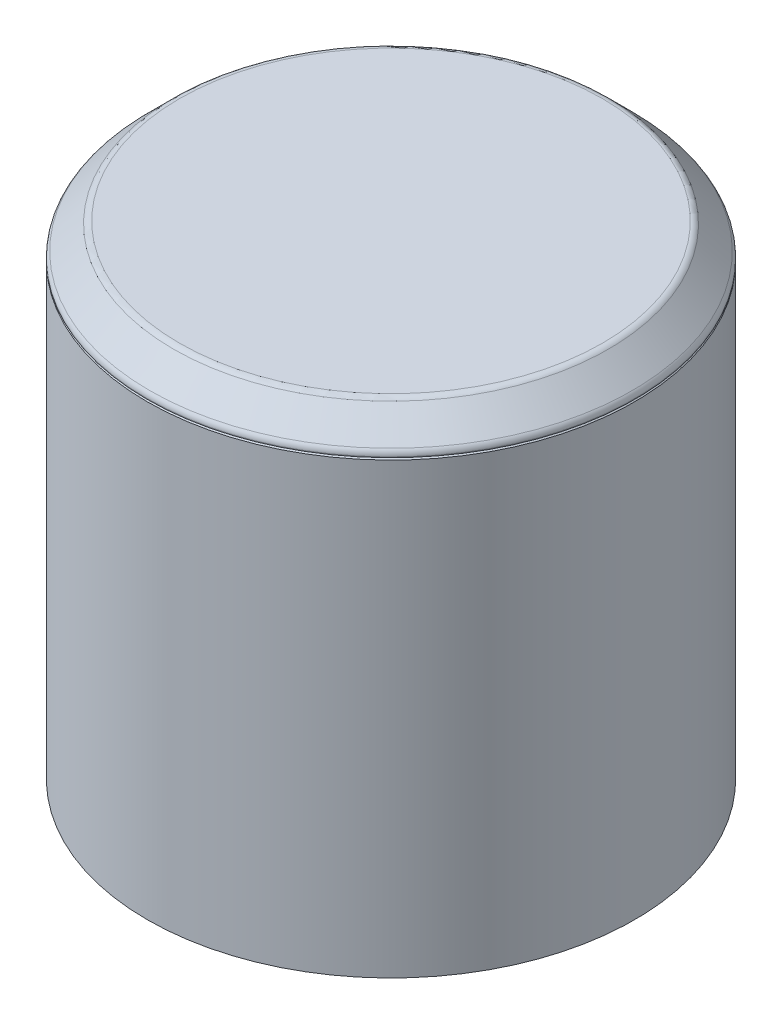
SolidWorks part; units mm, degrees
ref_plane "Ön Düzlem" through (0, 0, 0) normal (0, 0, 1) x (1, 0, 0)
ref_plane "Üst Düzlem" through (0, 0, 0) normal (0, 1, 0) x (1, 0, 0)
ref_plane "Sağ Düzlem" through (0, 0, 0) normal (1, 0, 0) x (0, 0, -1)
sketch "Çizim1" plane through (0, 0, 0) normal (1, 0, 0) x (0, 0, -1)
  line L1 (0, 0) -> (-59.5, 0)
  line L2 (0, 0) -> (0, 110)
  line L3 (0, 110) -> (-59.5, 110)
  line L4 (-59.5, 0) -> (-59.5, 110)
  line L5 (0, 0) -> (-45, 0)
  line L6 (0, 0) -> (0, -7)
  line L7 (0, -7) -> (-45, -7)
  line L8 (-45, 0) -> (-45, -7)
  dimension "D1" = 59.5
  dimension "D2" = 110
  dimension "D3" = 7
  dimension "D4" = 45
revolve "Döndür1" add sketch "Çizim1" angle 360 about L2 region at (0, -3.5, 22.5) region at (0, 55, 29.75)
sketch "Çizim2" plane through (0, 110, 0) normal (0, 1, 0) x (1, 0, 0)
  circle A0 centre (0, 0) radius 59.5
extrude "Yükseklik-Ekstrüzyon1" add sketch "Çizim2" along normal blind 8 separate body
chamfer "Pah1" distance 0.5 angle 45 1 edges at (0, 110, -59.5)
chamfer "Pah2" distance 7 angle 45 1 edges at (0, 118, 59.5)
fillet "Radyus1" radius 2 2 edges at (0, 111, 59.5) (0, 118, 52.5)
